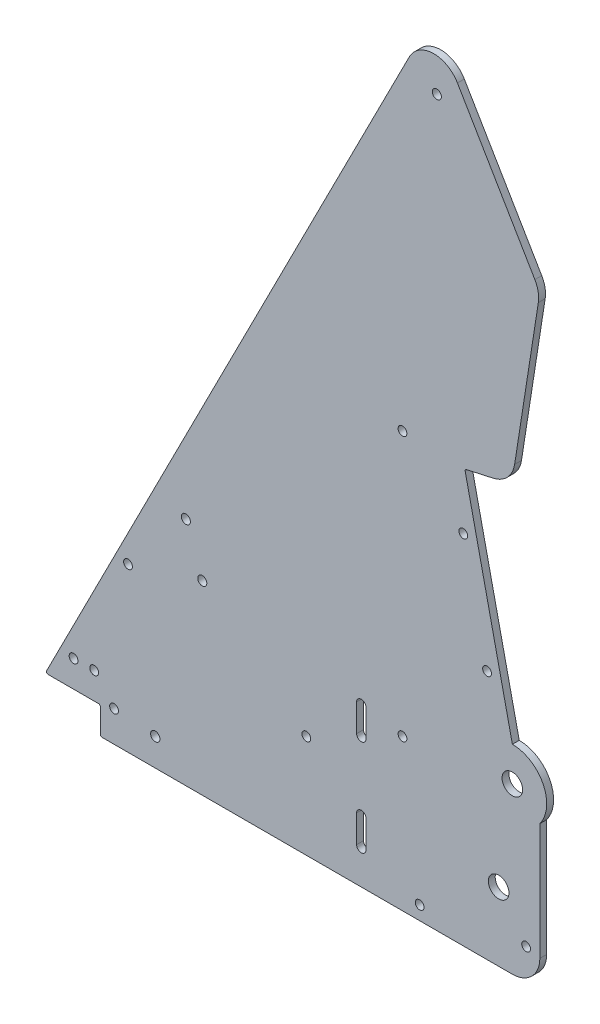
SolidWorks part; units mm, degrees
other "Markup1"
sketch "Sketch5"
ref_plane "Front Plane" through (0, 0, 0) normal (0, 0, 1) x (1, 0, 0)
ref_plane "Top Plane" through (0, 0, 0) normal (0, 1, 0) x (1, 0, 0)
ref_plane "Right Plane" through (0, 0, 0) normal (1, 0, 0) x (0, 0, -1)
sketch "Sketch1" plane through (0, 0, 0) normal (0, 0, 1) x (1, 0, 0)
  line L1 (228.6, -12.7) -> (228.6, 53.975)
  line L2 (178.7547, 351.4131) -> (0, 0)
  line L3 (228.6, 266.7) -> (178.7547, 351.4131)
  line L5 (0, 0) -> (25.4, 0)
  line L6 (25.4, 0) -> (25.4, -12.7)
  line L7 (25.4, -12.7) -> (228.6, -12.7)
  line L9 (215.9, 79.375) -> (193.9097, 178.5667)
  line L10 (193.9097, 178.5667) -> (215.6079, 183.377)
  line L11 (215.6079, 183.377) -> (228.6, 266.7)
  arc A0 (228.6, 53.975) -> (215.9, 79.375) centre (215.9, 63.5) ccw
  dimension "D7" = 12.7
  dimension "D8" = 76.2
  dimension "D10" = 31.75
  dimension "D2" = 279.4
  dimension "D3" = 25.4
  dimension "D4" = 215.9
  dimension "D5" = 394.2644
  dimension "D6" = 203.2
  dimension "D9" = 63.039
  dimension "D11" = 101.6
  dimension "D12" = 12.5
  dimension "D13" = 22.225
extrude "Boss-Extrude1" add sketch "Sketch1" along normal blind 3.175
sketch "Sketch2" plane through (0, 0, 3.175) normal (0, 0, 1) x (1, 0, 0)
  line L0 (178.7547, 351.4131) -> (0, 0) construction
  line L1 (25.4, -12.7) -> (228.6, -12.7) construction
  line L2 (215.9, 79.375) -> (193.9097, 178.5667) construction
  line L3 (193.9097, 178.5667) -> (215.6079, 183.377) construction
  line L4 (215.9, 79.375) -> (193.9097, 178.5667) construction
  line L5 (64.9432, 94.0578) -> (72.5445, 73.1732) construction
  line L6 (64.9432, 94.0578) -> (89.8317, 94.0578) construction
  line L10 (228.6, -12.7) -> (228.6, 53.975) construction
  circle A0 centre (64.9432, 94.0578) radius 2.0955
  circle A1 centre (180.975, 322.1643) radius 2.0955
  circle A2 centre (72.5445, 73.1732) radius 2.0955
  circle A3 centre (193.2078, 152.3944) radius 2.032
  circle A4 centre (215.9, 63.5) radius 4.7625
  circle A7 centre (173.0375, -6.35) radius 2.032
  circle A8 centre (204.203, 102.7985) radius 2.032
  circle A26 centre (209.55, 19.05) radius 4.7625
  arc A30 (228.6, 53.975) -> (215.9, 79.375) centre (215.9, 63.5) ccw construction
  circle A31 centre (165.1, 179.3875) radius 2.032
  dimension "D3" = 4.191
  dimension "D5" = 4.191
  dimension "D9" = 4.191
  dimension "D20" = 9.525
  dimension "D23" = 9.525
  dimension "D18" = 4.064
  dimension "D26" = 4.064
  dimension "D14" = 4.064
  dimension "D2" = 15.24
  dimension "D6" = 15.24
  dimension "D7" = 22.225
  dimension "D21" = 44.45
  dimension "D22" = 6.35
  dimension "D19" = 160.3375
  dimension "D24" = 44.45
  dimension "D25" = 6.35
  dimension "D27" = 25.4
  dimension "D28" = 50.8
  dimension "D29" = 6.35
  dimension "D17" = 6.35
  dimension "D33" = 55.5625
  dimension "D15" = 114.3
  dimension "D4" = 180.975
  dimension "D8" = 70
extrude "Cut-Extrude1" cut sketch "Sketch2" against normal through all
sketch "Sketch7" plane through (0, 0, 3.175) normal (0, 0, 1) x (1, 0, 0)
  line L0 (146.05, 3.175) -> (146.05, 15.875) construction
  line L1 (143.891, 3.175) -> (143.891, 15.875)
  line L2 (148.209, 3.175) -> (148.209, 15.875)
  line L3 (146.05, 47.625) -> (146.05, 60.325) construction
  line L4 (143.891, 47.625) -> (143.891, 60.325)
  line L5 (148.209, 47.625) -> (148.209, 60.325)
  line L6 (25.4, -12.7) -> (228.6, -12.7) construction
  line L12 (228.6, -12.7) -> (228.6, 53.975) construction
  line L13 (25.4, -12.7) -> (228.6, -12.7) construction
  arc A0 (143.891, 3.175) -> (148.209, 3.175) centre (146.05, 3.175) ccw
  arc A1 (148.209, 15.875) -> (143.891, 15.875) centre (146.05, 15.875) ccw
  arc A2 (143.891, 47.625) -> (148.209, 47.625) centre (146.05, 47.625) ccw
  arc A3 (148.209, 60.325) -> (143.891, 60.325) centre (146.05, 60.325) ccw
  circle A8 centre (50.8, 0) radius 2.159
  point P2 (146.05, 9.525)
  point P9 (146.05, 53.975)
  dimension "D1" = 4.318
  dimension "D5" = 4.318
  dimension "D2" = 12.7
  dimension "D3" = 12.7
  dimension "D4" = 44.45
  dimension "D6" = 95.25
  dimension "D7" = 82.55
  dimension "D8" = 15.875
  dimension "D9" = 12.7
extrude "Cut-Extrude2" cut sketch "Sketch7" against normal through all
sketch "Sketch10" plane through (0, 0, 3.175) normal (0, 0, 1) x (1, 0, 0)
  circle A1 centre (165.1, 57.15) radius 2.032
  circle A2 centre (120.65, 34.925) radius 2.032
  circle A3 centre (13.0465, 12.3347) radius 2.032
  circle A4 centre (22.5715, 12.3347) radius 2.032
  circle A5 centre (38.2114, 62.6398) radius 2.032
  dimension "D1" = 4.064
  dimension "D2" = 4.064
  dimension "D4" = 63.5
  dimension "D5" = 69.85
extrude "Cut-Extrude3" cut sketch "Sketch10" against normal up to next
fillet "Fillet1" radius 12.7 4 edges at (228.6, -12.7, 1.5875) (178.7547, 351.4131, 1.5875) (215.6079, 183.377, 1.5875) (228.6, 266.7, 1.5875)
fillet "Fillet2" radius 0.7937 4 edges at (25.4, -12.7, 1.5875) (25.4, 0, 1.5875) (193.9097, 178.5667, 1.5875) (0, 0, 1.5875)
sketch "Sketch12" plane through (0, 0, 3.175) normal (0, 0, 1) x (1, 0, 0)
  circle A0 centre (31.75, 1.5875) radius 2.032
  circle A1 centre (222.25, 1.5875) radius 2.032
  dimension "D1" = 4.064
extrude "Cut-Extrude5" cut sketch "Sketch12" against normal through all
equation "\"D6@Sketch2\"=\"D2@Sketch2\""
